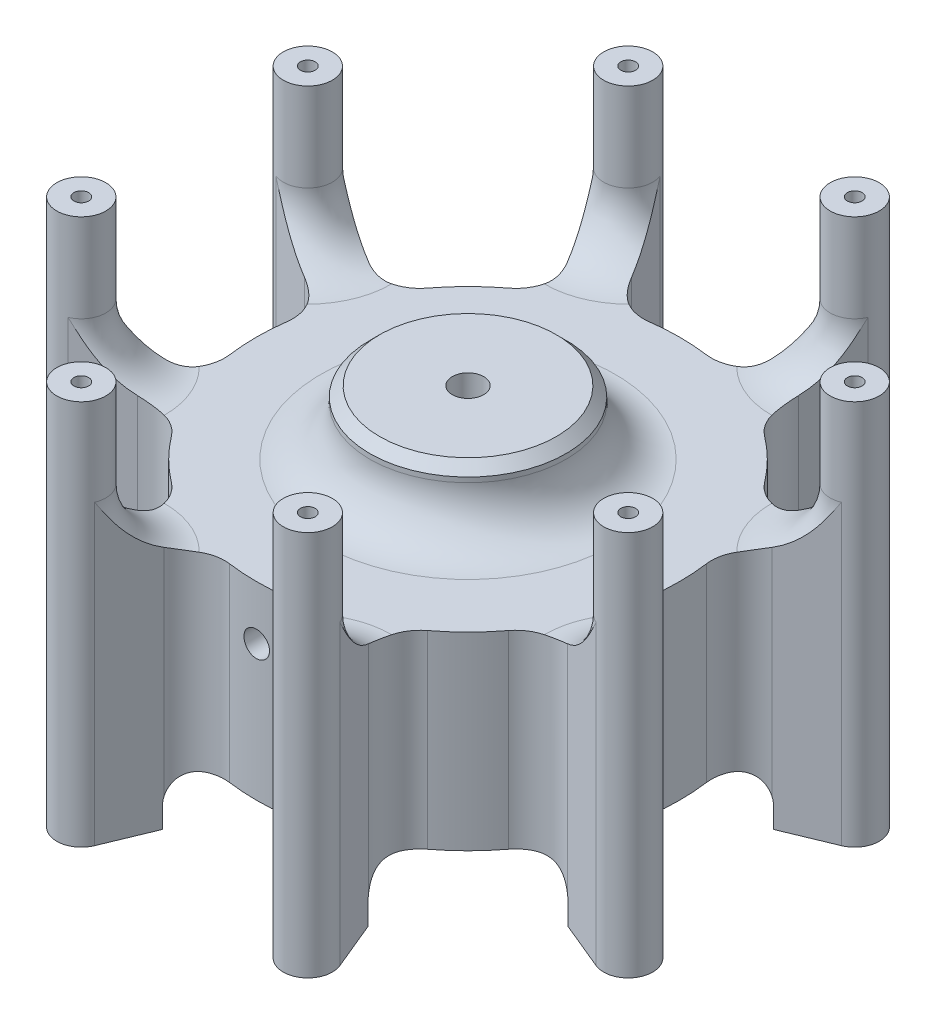
SolidWorks part; units mm, degrees
material "ABS"
ref_plane "前视基准面" through (0, 0, 0) normal (0, 0, 1) x (1, 0, 0)
ref_plane "上视基准面" through (0, 0, 0) normal (0, 1, 0) x (1, 0, 0)
ref_plane "右视基准面" through (0, 0, 0) normal (1, 0, 0) x (0, 0, -1)
sketch "Sketch1" plane through (0, 0, 0) normal (0, 1, 0) x (1, 0, 0)
  line L0 (0, 0) -> (27.8609, 11.5403) construction
  line L1 (0, 0) -> (37.476, -15.5231) construction
  line L2 (23.7983, 7.1516) -> (28.8176, 9.2307)
  line L3 (23.7983, -7.1516) -> (28.8176, -9.2307)
  line L4 (0, 0) -> (40.5637, 0) construction
  line L5 (28.8176, 9.2307) -> (26.9042, 13.85) construction
  line L6 (21.8849, -11.771) -> (26.9042, -13.85)
  line L7 (11.771, -21.8849) -> (13.85, -26.9042)
  line L8 (7.1516, -23.7983) -> (9.2307, -28.8176)
  line L9 (-7.1516, -23.7983) -> (-9.2307, -28.8176)
  line L10 (-11.771, -21.8849) -> (-13.85, -26.9042)
  line L11 (-21.8849, -11.771) -> (-26.9042, -13.85)
  line L12 (-23.7983, -7.1516) -> (-28.8176, -9.2307)
  line L13 (-23.7983, 7.1516) -> (-28.8176, 9.2307)
  line L14 (-21.8849, 11.771) -> (-26.9042, 13.85)
  line L15 (-11.771, 21.8849) -> (-13.85, 26.9042)
  line L16 (-7.1516, 23.7983) -> (-9.2307, 28.8176)
  line L17 (7.1516, 23.7983) -> (9.2307, 28.8176)
  line L18 (11.771, 21.8849) -> (13.85, 26.9042)
  line L19 (21.8849, 11.771) -> (26.9042, 13.85)
  circle A0 centre (0, 0) radius 40.5637 construction
  circle A1 centre (0, 0) radius 31.0637 construction
  arc A2 (28.8176, 9.2307) -> (28.8176, -9.2307) centre (31.0637, 0) ccw construction
  circle A3 centre (0, 0) radius 21.5637 construction
  arc A5 (21.3657, 2.9153) -> (21.3657, -2.9153) centre (0, 0) cw
  arc A6 (23.7983, 7.1516) -> (21.3657, 2.9153) centre (25.329, 3.4561) ccw
  arc A7 (23.7983, -7.1516) -> (21.3657, -2.9153) centre (25.329, -3.4561) cw
  arc A8 (28.8176, 9.2307) -> (26.9042, 13.85) centre (27.8609, 11.5403) ccw
  arc A9 (26.9042, -13.85) -> (28.8176, -9.2307) centre (27.8609, -11.5403) ccw
  arc A10 (21.8849, -11.771) -> (17.1693, -13.0464) centre (20.3541, -15.4665) ccw
  arc A11 (17.1693, -13.0464) -> (13.0464, -17.1693) centre (0, 0) cw
  arc A12 (11.771, -21.8849) -> (13.0464, -17.1693) centre (15.4665, -20.3541) cw
  arc A13 (9.2307, -28.8176) -> (13.85, -26.9042) centre (11.5403, -27.8609) ccw
  arc A14 (7.1516, -23.7983) -> (2.9153, -21.3657) centre (3.4561, -25.329) ccw
  arc A15 (2.9153, -21.3657) -> (-2.9153, -21.3657) centre (0, 0) cw
  arc A16 (-7.1516, -23.7983) -> (-2.9153, -21.3657) centre (-3.4561, -25.329) cw
  arc A17 (-13.85, -26.9042) -> (-9.2307, -28.8176) centre (-11.5403, -27.8609) ccw
  arc A18 (-11.771, -21.8849) -> (-13.0464, -17.1693) centre (-15.4665, -20.3541) ccw
  arc A19 (-13.0464, -17.1693) -> (-17.1693, -13.0464) centre (0, 0) cw
  arc A20 (-21.8849, -11.771) -> (-17.1693, -13.0464) centre (-20.3541, -15.4665) cw
  arc A21 (-28.8176, -9.2307) -> (-26.9042, -13.85) centre (-27.8609, -11.5403) ccw
  arc A22 (-23.7983, -7.1516) -> (-21.3657, -2.9153) centre (-25.329, -3.4561) ccw
  arc A23 (-21.3657, -2.9153) -> (-21.3657, 2.9153) centre (0, 0) cw
  arc A24 (-23.7983, 7.1516) -> (-21.3657, 2.9153) centre (-25.329, 3.4561) cw
  arc A25 (-26.9042, 13.85) -> (-28.8176, 9.2307) centre (-27.8609, 11.5403) ccw
  arc A26 (-21.8849, 11.771) -> (-17.1693, 13.0464) centre (-20.3541, 15.4665) ccw
  arc A27 (-17.1693, 13.0464) -> (-13.0464, 17.1693) centre (0, 0) cw
  arc A28 (-11.771, 21.8849) -> (-13.0464, 17.1693) centre (-15.4665, 20.3541) cw
  arc A29 (-9.2307, 28.8176) -> (-13.85, 26.9042) centre (-11.5403, 27.8609) ccw
  arc A30 (-7.1516, 23.7983) -> (-2.9153, 21.3657) centre (-3.4561, 25.329) ccw
  arc A31 (-2.9153, 21.3657) -> (2.9153, 21.3657) centre (0, 0) cw
  arc A32 (7.1516, 23.7983) -> (2.9153, 21.3657) centre (3.4561, 25.329) cw
  arc A33 (13.85, 26.9042) -> (9.2307, 28.8176) centre (11.5403, 27.8609) ccw
  arc A34 (11.771, 21.8849) -> (13.0464, 17.1693) centre (15.4665, 20.3541) ccw
  arc A35 (13.0464, 17.1693) -> (17.1693, 13.0464) centre (0, 0) cw
  arc A36 (21.8849, 11.771) -> (17.1693, 13.0464) centre (20.3541, 15.4665) cw
  point P15 (20.7446, 5.8867)
  point P21 (20.7446, -5.8867)
  point P23 (8.031, 15.215)
  point P24 (24.8414, 7.5749)
  point P27 (29.4394, 9.5)
  point P37 (27.877, 8.841)
  point P47 (26.98, 8.4695)
  point P57 (27.1769, 8.5511)
  point P67 (27.7848, 8.8029)
  point P77 (27.9362, 8.8656)
  point P84 (27.8504, 8.83)
  point P87 (28.9599, 9.4289)
  point P93 (0, 0)
  point P94 (28.9509, 9.2859)
  point P95 (28.3561, 9.0395)
  point P96 (28.8983, 9.2641)
  point P97 (28.8176, 9.2307)
  dimension "D1" = 2.5
  dimension "D2" = 19
  dimension "D5" = 81.1274
  dimension "D6" = 62.1274
  dimension "D7" = 4
  dimension "D8" = 4
  dimension "D4" = 45
  dimension "D3" = 2.5
  dimension "D9" = 8
extrude "Extrude1" add sketch "Sketch1" along normal blind 24.3
sketch "Sketch2" plane through (0, 0, 0) normal (0, -1, 0) x (1, 0, 0)
  circle A0 centre (27.8609, -11.5403) radius 1.55
  dimension "D1" = 3.1
extrude "Extrude2" add sketch "Sketch2" along normal blind 0.2
sketch "Sketch3" plane through (0, -0.2, 0) normal (0, -1, 0) x (-1, 0, 0)
  circle A0 centre (-27.8609, 11.5403) radius 0.75
  dimension "D1" = 1.5
extrude "Extrude3" cut sketch "Sketch3" against normal blind 50
ref_axis "Axis1" through (0, 31.55, 0) along (0, -1, 0)
pattern_circular "CirPattern1" count 8 every 45 about axis through (0, 0, 0) along (0, 1, 0) of "Extrude2", "Extrude3"
sketch "Sketch4" plane through (0, 24.3, 0) normal (0, 1, 0) x (1, 0, 0)
  circle A0 centre (27.8609, -11.5403) radius 2.5
  circle A1 centre (27.8609, -11.5403) radius 0.75
extrude "Extrude4" add sketch "Sketch4" along normal blind 15
fillet "Fillet1" radius 6 1 edges at (25.5512, 24.3, 10.5836)
pattern_circular "CirPattern3" count 8 every 45 about axis through (0, 31.55, 0) along (0, -1, 0) of "Extrude4"
fillet "Fillet2" radius 6 7 edges at (25.5512, 24.3, -10.5836) (10.5836, 24.3, -25.5512) (-10.5836, 24.3, -25.5512) (-25.5512, 24.3, -10.5836) (-25.5512, 24.3, 10.5836) (-10.5836, 24.3, 25.5512) (10.5836, 24.3, 25.5512)
sketch "Sketch6" plane through (0, 0, 0) normal (0, 0, 1) x (1, 0, 0)
  line L0 (0, 16.3) -> (0, 0)
  line L1 (0, 31.55) -> (0, -2.55) construction
  line L2 (0, 0) -> (-25, 0)
  line L3 (-21.8849, 0) -> (-17.1693, 0) construction
  line L4 (-25, 0) -> (-25, 2)
  line L5 (-22, 5) -> (-20, 5)
  line L6 (-17, 8) -> (-17, 13.3)
  line L7 (-14, 16.3) -> (0, 16.3)
  line L8 (2.9153, 24.3) -> (-2.9153, 24.3) construction
  arc A0 (-25, 2) -> (-22, 5) centre (-22, 2) cw
  arc A1 (-20, 5) -> (-17, 8) centre (-20, 8) ccw
  arc A2 (-17, 13.3) -> (-14, 16.3) centre (-14, 13.3) cw
  point P15 (-25, 5)
  point P18 (-17, 5)
  dimension "D5" = 3
  dimension "D6" = 3
  dimension "D1" = 8
  dimension "D2" = 5
  dimension "D3" = 17
  dimension "D4" = 8
revolve "Cut-Revolve1" cut sketch "Sketch6" angle 360 about axis through (0, 31.55, 0) along (0, -1, 0)
sketch "Sketch8" plane through (0, 24.3, 0) normal (0, 1, 0) x (1, 0, 0)
  line L0 (-1.6733, 2.55) -> (1.6733, 2.55)
  line L1 (1.0198, 2.5) -> (-1.0198, 2.5) construction
  arc A0 (-1.6733, 2.55) -> (1.6733, 2.55) centre (0, 0) ccw
  point P7 (0, 0)
  point P8 (-1.6733, 2.55)
  dimension "D1" = 6.1
  dimension "D2" = 0.05
extrude "Cut-Extrude1" cut sketch "Sketch8" against normal blind 15
sketch "Sketch10" plane through (0, 0, 0) normal (0, 0, 1) x (1, 0, 0)
  circle A1 centre (0, 18.8) radius 1.5
  dimension "D1" = 3
extrude "Cut-Extrude5" cut sketch "Sketch10" against normal blind 33
sketch "Sketch11" plane through (0, 0, 0) normal (0, 0, 1) x (1, 0, 0)
  circle A0 centre (0, 18.8) radius 1.3
  dimension "D1" = 2.6
extrude "Cut-Extrude6" cut sketch "Sketch11" along normal blind 29
ref_plane "Plane2" through (0, 0, -6) normal (0, 0, 1) x (1, 0, 0)
sketch "Sketch12" plane through (0, 0, -6) normal (0, 0, 1) x (1, 0, 0)
  circle A0 centre (0, 18.8) radius 3.25
  dimension "D1" = 6.5
extrude "Cut-Extrude7" cut sketch "Sketch12" against normal blind 29
sketch "Sketch13" plane through (0, 24.3, 0) normal (0, 1, 0) x (1, 0, 0)
  line L0 (1.6733, 2.55) -> (-1.6733, 2.55) construction
  line L1 (1.6733, 2.55) -> (-1.6733, 2.55)
  circle A0 centre (0, 0) radius 10
  arc A1 (-1.6733, 2.55) -> (1.6733, 2.55) centre (0, 0) ccw construction
  arc A2 (-1.6733, 2.55) -> (1.6733, 2.55) centre (0, 0) ccw
  dimension "D1" = 20
extrude "Extrude5" add sketch "Sketch13" along normal up to vertex (3.5 mm away)
sketch "Sketch14" plane through (0, 27.8, 0) normal (0, 1, 0) x (1, 0, 0)
  circle A0 centre (0, 0) radius 10 construction
  circle A1 centre (0, 0) radius 10
  circle A2 centre (0, 0) radius 1.6
  dimension "D1" = 3.2
extrude "Extrude6" add sketch "Sketch14" along normal blind 3
fillet "Fillet3" radius 5 1 edges at (0, 24.3, 10)
chamfer "Chamfer1" distance 1 angle 45 1 edges at (0, 30.8, 10)
